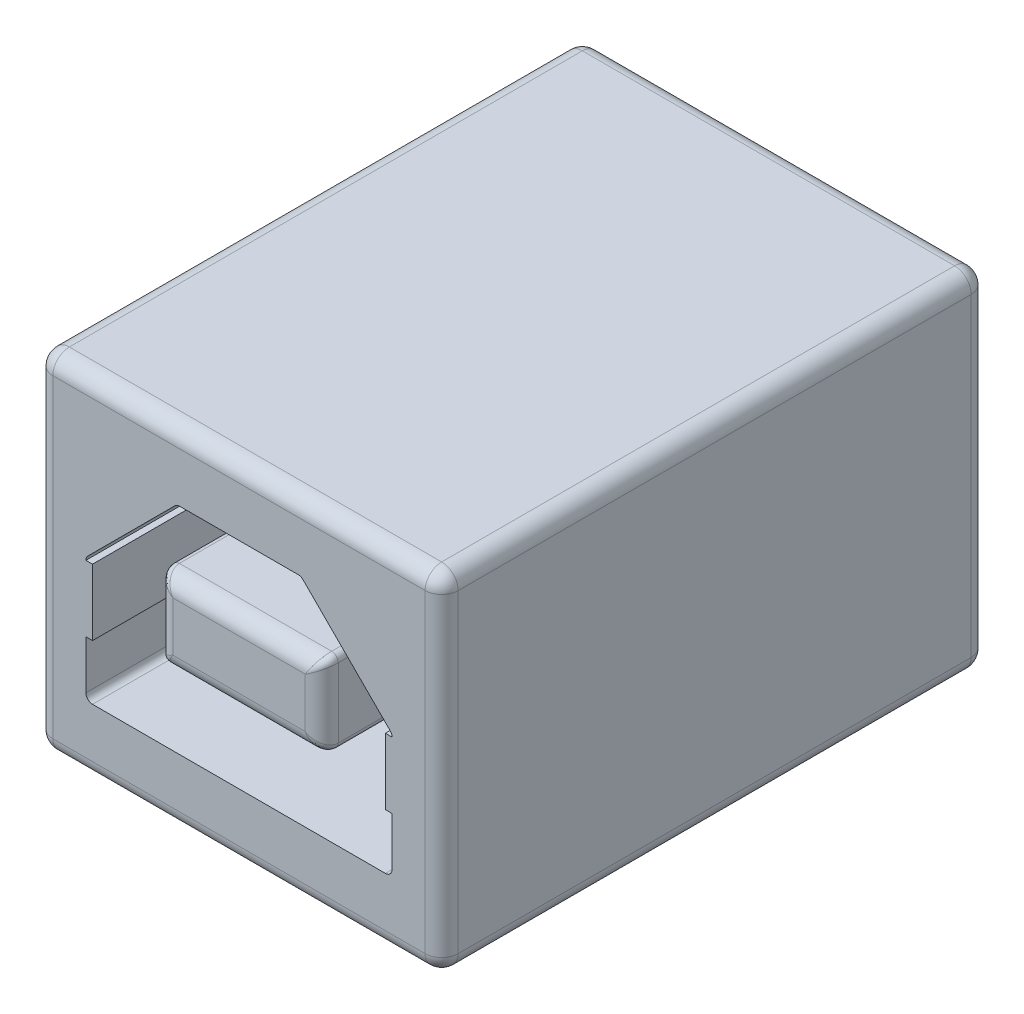
SolidWorks part; units mm, degrees
ref_plane "Front Plane" through (0, 0, 0) normal (0, 0, 1) x (1, 0, 0)
ref_plane "Top Plane" through (0, 0, 0) normal (0, 1, 0) x (1, 0, 0)
ref_plane "Right Plane" through (0, 0, 0) normal (1, 0, 0) x (0, 0, -1)
sketch "Sketch1" plane through (0, 0, 0) normal (0, 0, 1) x (1, 0, 0)
  line L1 (-6.125, -5.25) -> (6.125, -5.25)
  line L2 (-6.125, -5.25) -> (-6.125, 5.25)
  line L3 (-6.125, 5.25) -> (6.125, 5.25)
  line L4 (6.125, -5.25) -> (6.125, 5.25)
  line L5 (-6.125, -5.25) -> (6.125, 5.25) construction
  line L6 (-6.125, 5.25) -> (6.125, -5.25) construction
  point P0 (0, 0)
  dimension "D1" = 12.25
  dimension "D2" = 10.5
extrude "Boss-Extrude1" add sketch "Sketch1" against normal blind 16.5
sketch "Sketch2" plane through (0, 0, 0) normal (0, 0, 1) x (1, 0, 0)
  line L0 (-4.5664, 0.5586) -> (-1.9336, 3.1914)
  line L1 (-4.425, -3.25) -> (4.425, -3.25)
  line L2 (-4.625, -3.05) -> (-4.625, 0.4172)
  line L3 (-1.7922, 3.25) -> (1.7922, 3.25)
  line L4 (4.625, -3.05) -> (4.625, 0.4172)
  line L5 (-4.625, -3.25) -> (4.625, 3.25) construction
  line L6 (-4.625, 3.25) -> (4.625, -3.25) construction
  line L7 (1.9336, 3.1914) -> (4.5664, 0.5586)
  line L8 (-6.125, 5.25) -> (-6.125, -5.25) construction
  line L10 (-2.3, 1.25) -> (2.3, 1.25)
  line L11 (-2.5, 1.05) -> (-2.5, -1.05)
  line L12 (-2.3, -1.25) -> (2.3, -1.25)
  line L13 (2.5, 1.05) -> (2.5, -1.05)
  line L14 (-2.5, 1.25) -> (2.5, -1.25) construction
  line L15 (-2.5, -1.25) -> (2.5, 1.25) construction
  arc A0 (2.3, -1.25) -> (2.5, -1.05) centre (2.3, -1.05) ccw
  arc A1 (2.3, 1.25) -> (2.5, 1.05) centre (2.3, 1.05) cw
  arc A2 (4.5664, 0.5586) -> (4.625, 0.4172) centre (4.425, 0.4172) cw
  arc A3 (4.425, -3.25) -> (4.625, -3.05) centre (4.425, -3.05) ccw
  arc A4 (-4.425, -3.25) -> (-4.625, -3.05) centre (-4.425, -3.05) cw
  arc A5 (-2.5, -1.05) -> (-2.3, -1.25) centre (-2.3, -1.05) ccw
  arc A6 (-2.3, 1.25) -> (-2.5, 1.05) centre (-2.3, 1.05) ccw
  arc A7 (1.9336, 3.1914) -> (1.7922, 3.25) centre (1.7922, 3.05) ccw
  arc A8 (-1.9336, 3.1914) -> (-1.7922, 3.25) centre (-1.7922, 3.05) cw
  arc A9 (-4.5664, 0.5586) -> (-4.625, 0.4172) centre (-4.425, 0.4172) ccw
  point P0 (0, 0)
  point P12 (0, 0)
  point P25 (4.625, 0.5)
  point P40 (1.875, 3.25)
  point P43 (-1.875, 3.25)
  point P46 (-4.625, 0.5)
  dimension "D7" = 0.2
  dimension "D1" = 1.5
  dimension "D2" = 5
  dimension "D3" = 2.5
  dimension "D6" = 2
extrude "Cut-Extrude1" cut sketch "Sketch2" against normal blind 15
fillet "Fillet1" radius 0.5 32 edges at (-4.5664, -3.1914, -15) (-4.625, -1.3164, -15) (-4.6098, 0.4937, -15) (-3.25, 1.875, -15) (-1.8687, 3.2348, -15) (0, 3.25, -15) (1.8687, 3.2348, -15) (3.25, 1.875, -15) (4.6098, 0.4937, -15) (4.625, -1.3164, -15) (4.5664, -3.1914, -15) (0, -5.25, -16.5) (0, -5.25, 0) (-6.125, -5.25, -8.25) (-6.125, 0, -16.5) (-6.125, 0, 0) (6.125, 0, -16.5) (6.125, -5.25, -8.25) (6.125, 0, 0) (-6.125, 5.25, -8.25) (0, 5.25, -16.5) (6.125, 5.25, -8.25) (0, 5.25, 0) (0, -3.25, -15) (0, -1.25, 0) (-2.4414, -1.1914, 0) (-2.5, 0, 0) (-2.4414, 1.1914, 0) (0, 1.25, 0) (2.4414, 1.1914, 0) (2.5, 0, 0) (2.4414, -1.1914, 0)
sketch "Sketch3" plane through (4.625, 0, 0) normal (-1, 0, 0) x (0, 0, 1)
  line L0 (0, 4.75) -> (0, -4.75) construction
  line L1 (-7.5, 0.4172) -> (0, 0.4172)
  line L2 (-7.5, 0.4172) -> (-7.5, -1.5828)
  line L3 (-7.5, -1.5828) -> (0, -1.5828)
  line L4 (0, 0.4172) -> (0, -1.5828)
  line L5 (-14.5, 0.4172) -> (0, 0.4172) construction
  dimension "D1" = 2
  dimension "D2" = 7.5
extrude "Boss-Extrude2" add sketch "Sketch3" along normal blind 0.2
mirror "Mirror1" about plane through (0, 0, 0) normal (1, 0, 0) of "Boss-Extrude2"
